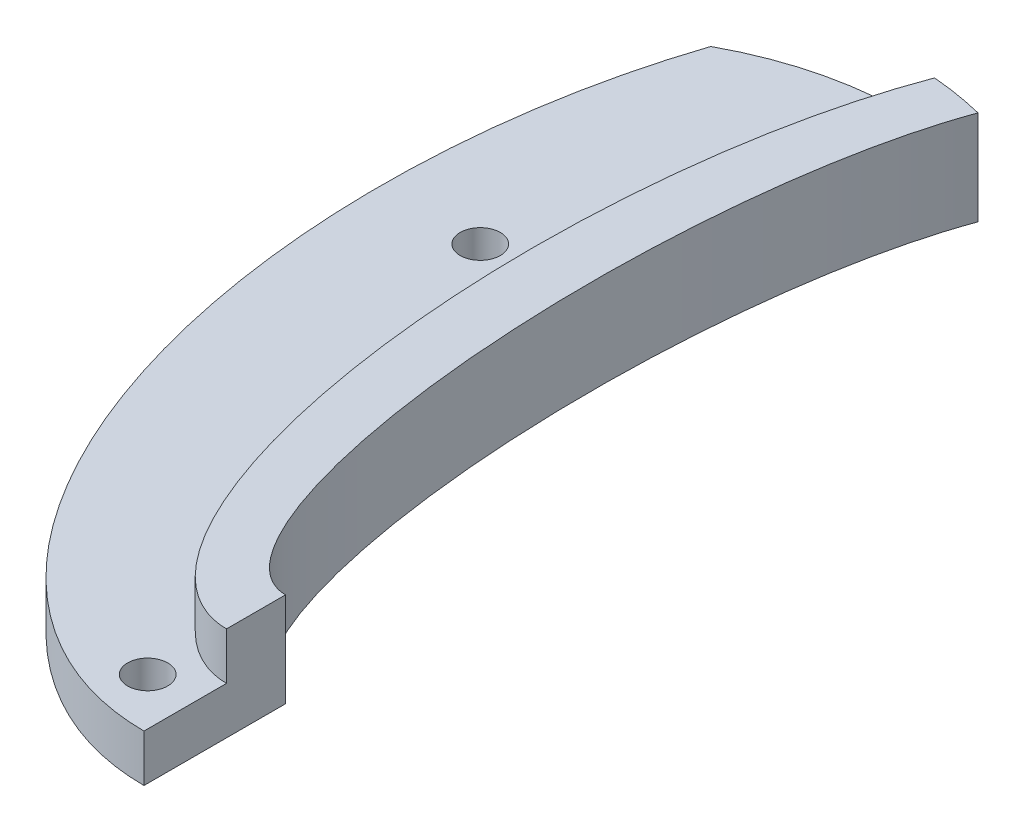
SolidWorks part; units mm, degrees
ref_plane "Спереди" through (0, 0, 0) normal (0, 0, 1) x (1, 0, 0)
ref_plane "Сверху" through (0, 0, 0) normal (0, 1, 0) x (1, 0, 0)
ref_plane "Справа" through (0, 0, 0) normal (1, 0, 0) x (0, 0, -1)
sketch "Эскиз1" plane through (0, 0, 0) normal (0, 1, 0) x (1, 0, 0)
  line L0 (0, -50) -> (0, -43)
  line L1 (0, 43) -> (0, 50) construction
  line L2 (0, 0) -> (-4.999, -57.1387) construction
  line L3 (0, 0) -> (-12.7544, -47.5999) construction
  line L5 (0, 0) -> (-46.6238, 0) construction
  circle A0 centre (-3.9973, -45.6893) radius 1.7
  arc A1 (-10.0001, 27.4752) -> (-26.23, 24.2663) centre (-13, 0) ccw
  circle A2 centre (-21.5, 0) radius 1.7
  ellipse E0 centre (0, 0) end of major axis (0, -43) minor radius 13 (-10.0001, 27.4752) -> (0, -43) ccw
  ellipse E1 centre (0, 0) end of major axis (0, -50) minor radius 30 (-26.23, 24.2663) -> (0, -50) ccw
  ellipse E2 centre (0, 0) end of major axis (0, -46.5) minor radius 21.5 (0, 46.5) -> (0, -46.5) ccw construction
  dimension "D1" = 43
  dimension "D10" = 3.4
  dimension "D11" = 3.4
  dimension "D2" = 13
  dimension "D3" = 30
  dimension "D4" = 50
  dimension "D5" = 21.5
  dimension "D6" = 46.5
  dimension "D7" = 5
  dimension "D8" = 15
extrude "Бобышка-Вытянуть1" add sketch "Эскиз1" along normal blind 4
sketch "Эскиз2" plane through (0, 4, 0) normal (0, 1, 0) x (1, 0, 0)
  line L0 (0, -38) -> (0, -43)
  arc A0 (-6.0296, 26.7198) -> (-10.4383, 27.4443) centre (-12.7011, -0.1013) ccw
  ellipse E0 centre (0, -2) end of major axis (0, -43) minor radius 15 (-10.4383, 27.4443) -> (0, -43) ccw
  ellipse E1 centre (0, -2) end of major axis (0, -38) minor radius 10 (-6.0296, 26.7198) -> (0, -38) ccw
  point P3 (0, 0)
  point P17 (0, 0)
  point P18 (0, 0)
  point P20 (0, 0)
  dimension "D3" = 5
  dimension "D1" = 36
  dimension "D2" = 5
  dimension "D4" = 10
extrude "Бобышка-Вытянуть2" add sketch "Эскиз2" along normal blind 4 and the other way blind 4
